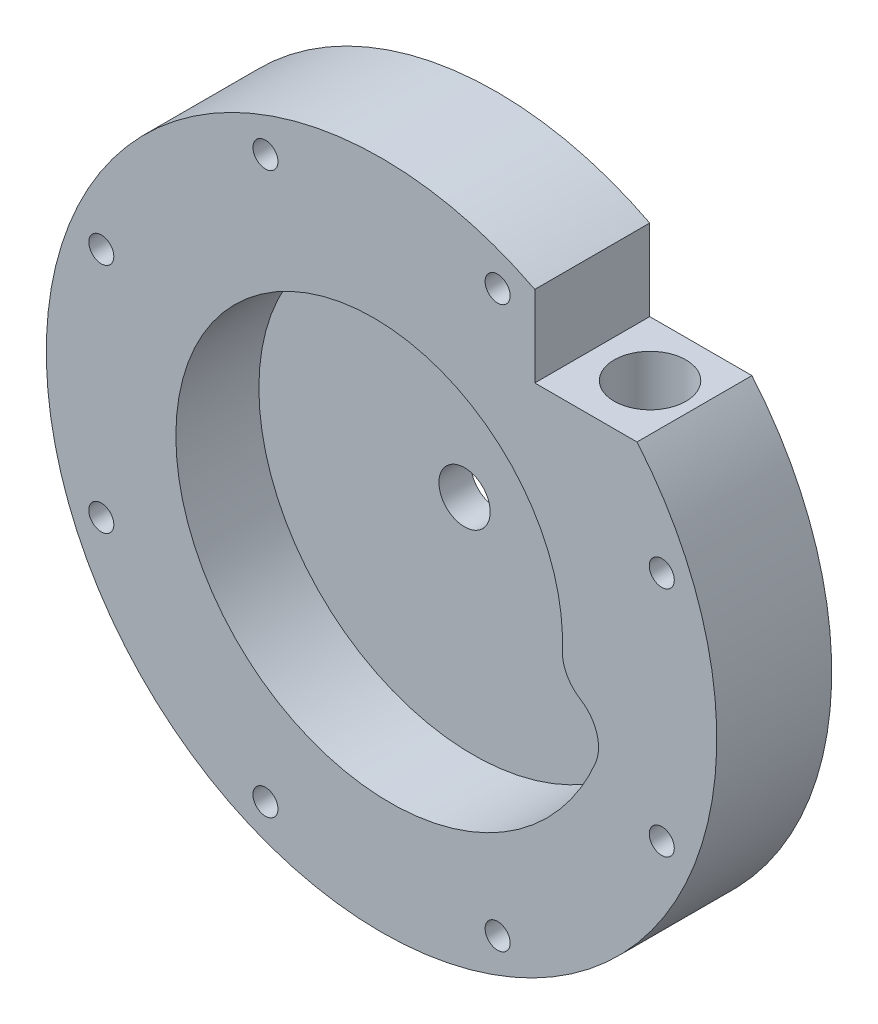
SolidWorks part; units mm, degrees
material "6061-T6 (SS)"
ref_plane "Front Plane" through (0, 0, 0) normal (0, 0, 1) x (1, 0, 0)
ref_plane "Top Plane" through (0, 0, 0) normal (0, 1, 0) x (1, 0, 0)
ref_plane "Right Plane" through (0, 0, 0) normal (1, 0, 0) x (0, 0, -1)
sketch "Sketch22" plane through (0, 0, 0) normal (0, 1, 0) x (1, 0, 0)
  line L0 (-25.4, 0) -> (-5.1, 0)
  line L1 (-25.4, 0) -> (-25.4, -16.51)
  line L2 (-17.4625, 6.35) -> (-17.4625, 4.7625)
  line L3 (-25.4, -16.51) -> (-66.675, -16.51)
  line L4 (-66.675, -16.51) -> (-66.675, 6.35)
  line L9 (-17.4625, 6.35) -> (-66.675, 6.35)
  line L10 (0, 0) -> (0, 9.525) construction
  line L11 (-5.1, 6.35) -> (-5.1, 0)
  line L12 (-17.4625, 4.7625) -> (-11.1125, 4.7625)
  line L15 (-11.1125, 4.7625) -> (-11.1125, 6.35)
  line L16 (-11.1125, 6.35) -> (-5.1, 6.35)
  line L17 (-25.4, -0.508) -> (-0.1653, -0.508) construction
  line L18 (-0.1653, -9.508) -> (-0.1653, -0.508) construction
  dimension "D5" = 50.8
  dimension "D6" = 133.35
  dimension "D7" = 10.2
  dimension "D2" = 6.35
  dimension "D4" = 22.225
  dimension "D8" = 1.5875
  dimension "D1" = 6.35
  dimension "D3" = 22.86
  dimension "D9" = 0.508
revolve "Main Body" add sketch "Sketch22" angle 360 about L10
curve "Volute Spiral"
  spline degree 3 poles (35.9487, 0, 0) (35.9516, 0.0754, 0) (35.9573, 0.2262, 0) (35.9642, 0.4524, 0) (35.9698, 0.6788, 0) (35.9739, 0.9052, 0) (35.9766, 1.1318, 0) (35.9779, 1.3583, 0) (35.9778, 1.585, 0) (35.9763, 1.8117, 0) (35.9733, 2.0385, 0) (35.969, 2.2653, 0) (35.9632, 2.4921, 0) (35.956, 2.7189, 0) (35.9473, 2.9457, 0) (35.9373, 3.1726, 0) (35.9258, 3.3994, 0) (35.9129, 3.6262, 0) (35.8986, 3.853, 0) (35.8828, 4.0798, 0) (35.8656, 4.3065, 0) (35.847, 4.5331, 0) (35.827, 4.7597, 0) (35.8055, 4.9862, 0) (35.7826, 5.2127, 0) (35.7583, 5.439, 0) (35.7326, 5.6653, 0) (35.7054, 5.8914, 0) (35.6768, 6.1174, 0) (35.6468, 6.3433, 0) (35.6153, 6.5691, 0) (35.5825, 6.7947, 0) (35.5482, 7.0201, 0) (35.5124, 7.2455, 0) (35.4753, 7.4706, 0) (35.4367, 7.6955, 0) (35.3967, 7.9203, 0) (35.3553, 8.1449, 0) (35.3125, 8.3692, 0) (35.2683, 8.5934, 0) (35.2226, 8.8173, 0) (35.1755, 9.041, 0) (35.127, 9.2644, 0) (35.0771, 9.4876, 0) (35.0257, 9.7105, 0) (34.973, 9.9332, 0) (34.9188, 10.1556, 0) (34.8633, 10.3777, 0) (34.8063, 10.5995, 0) (34.7479, 10.821, 0) (34.6881, 11.0422, 0) (34.6269, 11.263, 0) (34.5643, 11.4836, 0) (34.5004, 11.7037, 0) (34.435, 11.9236, 0) (34.3682, 12.1431, 0) (34.3, 12.3622, 0) (34.2304, 12.5809, 0) (34.1594, 12.7993, 0) (34.0871, 13.0172, 0) (34.0133, 13.2348, 0) (33.9382, 13.4519, 0) (33.8617, 13.6686, 0) (33.7838, 13.8849, 0) (33.7045, 14.1008, 0) (33.6238, 14.3162, 0) (33.5418, 14.5311, 0) (33.4584, 14.7456, 0) (33.3737, 14.9596, 0) (33.2875, 15.1732, 0) (33.2, 15.3862, 0) (33.1112, 15.5988, 0) (33.021, 15.8108, 0) (32.9294, 16.0223, 0) (32.8365, 16.2333, 0) (32.7422, 16.4438, 0) (32.6466, 16.6537, 0) (32.5497, 16.8631, 0) (32.4514, 17.0719, 0) (32.3517, 17.2801, 0) (32.2508, 17.4878, 0) (32.1485, 17.6949, 0) (32.0448, 17.9013, 0) (31.9399, 18.1072, 0) (31.8336, 18.3125, 0) (31.7261, 18.5171, 0) (31.6172, 18.7212, 0) (31.507, 18.9246, 0) (31.3955, 19.1273, 0) (31.2827, 19.3294, 0) (31.1685, 19.5308, 0) (31.0531, 19.7316, 0) (30.9365, 19.9317, 0) (30.8185, 20.1311, 0) (30.6992, 20.3298, 0) (30.5787, 20.5278, 0) (30.4569, 20.7251, 0) (30.3338, 20.9217, 0) (30.2094, 21.1175, 0) (30.0838, 21.3126, 0) (29.957, 21.507, 0) (29.8288, 21.7006, 0) (29.6995, 21.8935, 0) (29.5689, 22.0856, 0) (29.437, 22.2769, 0) (29.3039, 22.4674, 0) (29.1696, 22.6571, 0) (29.0341, 22.8461, 0) (28.8973, 23.0342, 0) (28.7593, 23.2215, 0) (28.6201, 23.408, 0) (28.4797, 23.5937, 0) (28.3381, 23.7785, 0) (28.1953, 23.9625, 0) (28.0514, 24.1456, 0) (27.9062, 24.3279, 0) (27.7598, 24.5093, 0) (27.6123, 24.6898, 0) (27.4636, 24.8694, 0) (27.3137, 25.0482, 0) (27.1627, 25.226, 0) (27.0105, 25.403, 0) (26.8572, 25.579, 0) (26.7027, 25.7541, 0) (26.5471, 25.9282, 0) (26.3903, 26.1015, 0) (26.2325, 26.2738, 0) (26.0735, 26.4451, 0) (25.9134, 26.6155, 0) (25.7521, 26.7849, 0) (25.5898, 26.9533, 0) (25.4264, 27.1208, 0) (25.2619, 27.2872, 0) (25.0963, 27.4527, 0) (24.9296, 27.6172, 0) (24.7618, 27.7806, 0) (24.593, 27.9431, 0) (24.4231, 28.1045, 0) (24.2521, 28.2649, 0) (24.0802, 28.4242, 0) (23.9071, 28.5825, 0) (23.733, 28.7398, 0) (23.5579, 28.896, 0) (23.3818, 29.0511, 0) (23.2046, 29.2052, 0) (23.0265, 29.3582, 0) (22.8473, 29.5101, 0) (22.6671, 29.6609, 0) (22.486, 29.8106, 0) (22.3038, 29.9592, 0) (22.1207, 30.1067, 0) (21.9366, 30.2531, 0) (21.7515, 30.3984, 0) (21.5655, 30.5425, 0) (21.3785, 30.6855, 0) (21.1906, 30.8274, 0) (21.0018, 30.9681, 0) (20.812, 31.1076, 0) (20.6213, 31.246, 0) (20.4297, 31.3833, 0) (20.2371, 31.5193, 0) (20.0437, 31.6542, 0) (19.8494, 31.7879, 0) (19.6541, 31.9204, 0) (19.458, 32.0517, 0) (19.2611, 32.1818, 0) (19.0632, 32.3106, 0) (18.8645, 32.4383, 0) (18.665, 32.5648, 0) (18.4646, 32.69, 0) (18.2634, 32.814, 0) (18.0613, 32.9368, 0) (17.8584, 33.0583, 0) (17.6547, 33.1786, 0) (17.4502, 33.2976, 0) (17.2449, 33.4154, 0) (17.0389, 33.5319, 0) (16.832, 33.6471, 0) (16.6244, 33.761, 0) (16.4159, 33.8737, 0) (16.2068, 33.9851, 0) (15.9969, 34.0952, 0) (15.7862, 34.204, 0) (15.5748, 34.3115, 0) (15.3627, 34.4177, 0) (15.1498, 34.5226, 0) (14.9363, 34.6262, 0) (14.722, 34.7285, 0) (14.5071, 34.8294, 0) (14.2914, 34.929, 0) (14.0751, 35.0273, 0) (13.8581, 35.1242, 0) (13.6405, 35.2198, 0) (13.4222, 35.3141, 0) (13.2032, 35.407, 0) (12.9836, 35.4985, 0) (12.7634, 35.5887, 0) (12.5426, 35.6775, 0) (12.3212, 35.765, 0) (12.0991, 35.8511, 0) (11.8765, 35.9358, 0) (11.6532, 36.0191, 0) (11.4294, 36.101, 0) (11.205, 36.1816, 0) (10.9801, 36.2607, 0) (10.7546, 36.3385, 0) (10.5286, 36.4148, 0) (10.302, 36.4898, 0) (10.0749, 36.5633, 0) (9.8473, 36.6355, 0) (9.6192, 36.7062, 0) (9.3906, 36.7755, 0) (9.1615, 36.8434, 0) (8.9319, 36.9098, 0) (8.7018, 36.9748, 0) (8.4713, 37.0384, 0) (8.2403, 37.1006, 0) (8.0089, 37.1613, 0) (7.777, 37.2206, 0) (7.5447, 37.2784, 0) (7.312, 37.3348, 0) (7.0789, 37.3897, 0) (6.8453, 37.4432, 0) (6.6114, 37.4952, 0) (6.3771, 37.5458, 0) (6.1424, 37.5949, 0) (5.9074, 37.6425, 0) (5.672, 37.6887, 0) (5.4362, 37.7334, 0) (5.2002, 37.7766, 0) (4.9637, 37.8183, 0) (4.727, 37.8586, 0) (4.49, 37.8974, 0) (4.2526, 37.9347, 0) (4.015, 37.9705, 0) (3.7771, 38.0048, 0) (3.5389, 38.0377, 0) (3.3004, 38.069, 0) (3.0617, 38.0989, 0) (2.8228, 38.1273, 0) (2.5836, 38.1541, 0) (2.3442, 38.1795, 0) (2.1046, 38.2034, 0) (1.8647, 38.2257, 0) (1.6247, 38.2466, 0) (1.3845, 38.2659, 0) (1.1441, 38.2838, 0) (0.9035, 38.3001, 0) (0.6628, 38.315, 0) (0.4219, 38.3283, 0) (0.1808, 38.3401, 0) (-0.0603, 38.3504, 0) (-0.3016, 38.3591, 0) (-0.543, 38.3664, 0) (-0.7845, 38.3721, 0) (-1.0261, 38.3764, 0) (-1.2677, 38.3791, 0) (-1.5095, 38.3802, 0) (-1.7513, 38.3799, 0) (-1.9932, 38.378, 0) (-2.2351, 38.3746, 0) (-2.477, 38.3697, 0) (-2.719, 38.3633, 0) (-2.961, 38.3554, 0) (-3.203, 38.3459, 0) (-3.445, 38.3349, 0) (-3.687, 38.3223, 0) (-3.929, 38.3083, 0) (-4.1709, 38.2927, 0) (-4.4128, 38.2756, 0) (-4.6546, 38.2569, 0) (-4.8964, 38.2368, 0) (-5.1381, 38.2151, 0) (-5.3798, 38.1919, 0) (-5.6213, 38.1671, 0) (-5.8628, 38.1408, 0) (-6.1041, 38.113, 0) (-6.3453, 38.0837, 0) (-6.5864, 38.0529, 0) (-6.8274, 38.0205, 0) (-7.0682, 37.9866, 0) (-7.3089, 37.9512, 0) (-7.5494, 37.9142, 0) (-7.7897, 37.8758, 0) (-8.0298, 37.8358, 0) (-8.2698, 37.7943, 0) (-8.5095, 37.7512, 0) (-8.749, 37.7067, 0) (-8.9883, 37.6606, 0) (-9.2274, 37.613, 0) (-9.4662, 37.5639, 0) (-9.7048, 37.5133, 0) (-9.9431, 37.4612, 0) (-10.1811, 37.4076, 0) (-10.4189, 37.3524, 0) (-10.6563, 37.2957, 0) (-10.8935, 37.2376, 0) (-11.1303, 37.1779, 0) (-11.3669, 37.1167, 0) (-11.6031, 37.054, 0) (-11.8389, 36.9898, 0) (-12.0745, 36.9241, 0) (-12.3096, 36.857, 0) (-12.5444, 36.7883, 0) (-12.7788, 36.7181, 0) (-13.0129, 36.6464, 0) (-13.2465, 36.5733, 0) (-13.4797, 36.4986, 0) (-13.7126, 36.4225, 0) (-13.9449, 36.3449, 0) (-14.1769, 36.2658, 0) (-14.4084, 36.1852, 0) (-14.6395, 36.1032, 0) (-14.8701, 36.0196, 0) (-15.1002, 35.9346, 0) (-15.3299, 35.8482, 0) (-15.559, 35.7602, 0) (-15.7877, 35.6708, 0) (-16.0159, 35.58, 0) (-16.2435, 35.4877, 0) (-16.4706, 35.3939, 0) (-16.6972, 35.2987, 0) (-16.9232, 35.202, 0) (-17.1487, 35.1039, 0) (-17.3736, 35.0043, 0) (-17.5979, 34.9033, 0) (-17.8217, 34.8009, 0) (-18.0448, 34.697, 0) (-18.2674, 34.5917, 0) (-18.4893, 34.485, 0) (-18.7107, 34.3769, 0) (-18.9314, 34.2673, 0) (-19.1514, 34.1563, 0) (-19.3708, 34.044, 0) (-19.5896, 33.9302, 0) (-19.8077, 33.815, 0) (-20.0251, 33.6984, 0) (-20.2419, 33.5804, 0) (-20.4579, 33.461, 0) (-20.6733, 33.3402, 0) (-20.8879, 33.218, 0) (-21.1018, 33.0945, 0) (-21.315, 32.9696, 0) (-21.5275, 32.8433, 0) (-21.7392, 32.7156, 0) (-21.9501, 32.5866, 0) (-22.1603, 32.4562, 0) (-22.3698, 32.3245, 0) (-22.5784, 32.1914, 0) (-22.7863, 32.057, 0) (-22.9933, 31.9212, 0) (-23.1996, 31.7841, 0) (-23.405, 31.6457, 0) (-23.6097, 31.5059, 0) (-23.8134, 31.3648, 0) (-24.0164, 31.2224, 0) (-24.2185, 31.0787, 0) (-24.4197, 30.9337, 0) (-24.6201, 30.7874, 0) (-24.8196, 30.6398, 0) (-25.0182, 30.4909, 0) (-25.216, 30.3407, 0) (-25.4128, 30.1892, 0) (-25.6087, 30.0365, 0) (-25.8037, 29.8825, 0) (-25.9978, 29.7272, 0) (-26.191, 29.5707, 0) (-26.3832, 29.4129, 0) (-26.5745, 29.2539, 0) (-26.7648, 29.0936, 0) (-26.9541, 28.9321, 0) (-27.1425, 28.7693, 0) (-27.3299, 28.6054, 0) (-27.5163, 28.4402, 0) (-27.7017, 28.2738, 0) (-27.8861, 28.1062, 0) (-28.0695, 27.9374, 0) (-28.2519, 27.7674, 0) (-28.4332, 27.5962, 0) (-28.6135, 27.4238, 0) (-28.7928, 27.2503, 0) (-28.971, 27.0756, 0) (-29.1482, 26.8997, 0) (-29.3243, 26.7227, 0) (-29.4993, 26.5445, 0) (-29.6733, 26.3652, 0) (-29.8461, 26.1847, 0) (-30.0179, 26.0031, 0) (-30.1885, 25.8204, 0) (-30.3581, 25.6366, 0) (-30.5265, 25.4516, 0) (-30.6938, 25.2656, 0) (-30.86, 25.0784, 0) (-31.025, 24.8902, 0) (-31.1889, 24.7009, 0) (-31.3516, 24.5105, 0) (-31.5132, 24.319, 0) (-31.6736, 24.1265, 0) (-31.8329, 23.9329, 0) (-31.9909, 23.7382, 0) (-32.1478, 23.5426, 0) (-32.3034, 23.3459, 0) (-32.4579, 23.1481, 0) (-32.6112, 22.9494, 0) (-32.7632, 22.7496, 0) (-32.914, 22.5489, 0) (-33.0636, 22.3471, 0) (-33.212, 22.1443, 0) (-33.3591, 21.9406, 0) (-33.505, 21.7359, 0) (-33.6496, 21.5302, 0) (-33.7929, 21.3236, 0) (-33.935, 21.116, 0) (-34.0758, 20.9075, 0) (-34.2154, 20.698, 0) (-34.3536, 20.4876, 0) (-34.4906, 20.2763, 0) (-34.6262, 20.0641, 0) (-34.7606, 19.851, 0) (-34.8936, 19.637, 0) (-35.0253, 19.4221, 0) (-35.1557, 19.2063, 0) (-35.2848, 18.9896, 0) (-35.4126, 18.7721, 0) (-35.539, 18.5537, 0) (-35.664, 18.3345, 0) (-35.7877, 18.1144, 0) (-35.9101, 17.8935, 0) (-36.0311, 17.6718, 0) (-36.1507, 17.4493, 0) (-36.2689, 17.2259, 0) (-36.3858, 17.0018, 0) (-36.5013, 16.7769, 0) (-36.6154, 16.5512, 0) (-36.7281, 16.3247, 0) (-36.8394, 16.0975, 0) (-36.9493, 15.8695, 0) (-37.0578, 15.6408, 0) (-37.1649, 15.4113, 0) (-37.2705, 15.1811, 0) (-37.3748, 14.9502, 0) (-37.4776, 14.7186, 0) (-37.5789, 14.4862, 0) (-37.6789, 14.2532, 0) (-37.7773, 14.0195, 0) (-37.8744, 13.7851, 0) (-37.97, 13.5501, 0) (-38.0641, 13.3144, 0) (-38.1567, 13.078, 0) (-38.2479, 12.8411, 0) (-38.3377, 12.6034, 0) (-38.4259, 12.3652, 0) (-38.5127, 12.1264, 0) (-38.598, 11.8869, 0) (-38.6818, 11.6469, 0) (-38.7641, 11.4062, 0) (-38.8449, 11.165, 0) (-38.9242, 10.9233, 0) (-39.002, 10.6809, 0) (-39.0783, 10.4381, 0) (-39.1531, 10.1947, 0) (-39.2264, 9.9507, 0) (-39.2982, 9.7063, 0) (-39.3684, 9.4613, 0) (-39.4371, 9.2159, 0) (-39.5043, 8.9699, 0) (-39.57, 8.7235, 0) (-39.6341, 8.4766, 0) (-39.6966, 8.2292, 0) (-39.7577, 7.9814, 0) (-39.8172, 7.7332, 0) (-39.8751, 7.4845, 0) (-39.9315, 7.2354, 0) (-39.9863, 6.9858, 0) (-40.0396, 6.7359, 0) (-40.0913, 6.4856, 0) (-40.1414, 6.2349, 0) (-40.19, 5.9838, 0) (-40.237, 5.7324, 0) (-40.2825, 5.4806, 0) (-40.3263, 5.2284, 0) (-40.3686, 4.976, 0) (-40.4093, 4.7232, 0) (-40.4484, 4.47, 0) (-40.486, 4.2166, 0) (-40.5219, 3.9629, 0) (-40.5563, 3.7089, 0) (-40.5891, 3.4546, 0) (-40.6203, 3.2001, 0) (-40.6498, 2.9453, 0) (-40.6778, 2.6902, 0) (-40.7042, 2.435, 0) (-40.729, 2.1795, 0) (-40.7522, 1.9237, 0) (-40.7738, 1.6678, 0) (-40.7937, 1.4117, 0) (-40.8121, 1.1554, 0) (-40.8289, 0.8989, 0) (-40.844, 0.6423, 0) (-40.8575, 0.3855, 0) (-40.8695, 0.1285, 0) (-40.8798, -0.1286, 0) (-40.8884, -0.3858, 0) (-40.8955, -0.6431, 0) (-40.901, -0.9005, 0) (-40.9048, -1.158, 0) (-40.907, -1.4156, 0) (-40.9076, -1.6733, 0) (-40.9066, -1.931, 0) (-40.9039, -2.1888, 0) (-40.8996, -2.4467, 0) (-40.8937, -2.7045, 0) (-40.8862, -2.9624, 0) (-40.8771, -3.2203, 0) (-40.8663, -3.4782, 0) (-40.8539, -3.7361, 0) (-40.8399, -3.994, 0) (-40.8242, -4.2519, 0) (-40.8069, -4.5097, 0) (-40.788, -4.7674, 0) (-40.7675, -5.0251, 0) (-40.7453, -5.2828, 0) (-40.7215, -5.5403, 0) (-40.6961, -5.7978, 0) (-40.669, -6.0552, 0) (-40.6404, -6.3124, 0) (-40.6101, -6.5695, 0) (-40.5781, -6.8265, 0) (-40.5446, -7.0834, 0) (-40.5094, -7.3401, 0) (-40.4726, -7.5967, 0) (-40.4342, -7.853, 0) (-40.3941, -8.1092, 0) (-40.3525, -8.3652, 0) (-40.3092, -8.621, 0) (-40.2643, -8.8766, 0) (-40.2177, -9.1319, 0) (-40.1696, -9.3871, 0) (-40.1198, -9.6419, 0) (-40.0684, -9.8966, 0) (-40.0154, -10.1509, 0) (-39.9608, -10.405, 0) (-39.9046, -10.6588, 0) (-39.8468, -10.9123, 0) (-39.7873, -11.1655, 0) (-39.7263, -11.4184, 0) (-39.6636, -11.6709, 0) (-39.5994, -11.9232, 0) (-39.5335, -12.175, 0) (-39.466, -12.4265, 0) (-39.397, -12.6777, 0) (-39.3263, -12.9285, 0) (-39.254, -13.1789, 0) (-39.1802, -13.4288, 0) (-39.1048, -13.6784, 0) (-39.0277, -13.9276, 0) (-38.9491, -14.1763, 0) (-38.8689, -14.4246, 0) (-38.7871, -14.6725, 0) (-38.7038, -14.9199, 0) (-38.6188, -15.1668, 0) (-38.5323, -15.4132, 0) (-38.4442, -15.6592, 0) (-38.3546, -15.9047, 0) (-38.2634, -16.1496, 0) (-38.1706, -16.3941, 0) (-38.0762, -16.638, 0) (-37.9803, -16.8813, 0) (-37.8829, -17.1242, 0) (-37.7839, -17.3664, 0) (-37.6833, -17.6081, 0) (-37.5812, -17.8492, 0) (-37.4776, -18.0898, 0) (-37.3724, -18.3297, 0) (-37.2657, -18.569, 0) (-37.1574, -18.8077, 0) (-37.0477, -19.0458, 0) (-36.9364, -19.2833, 0) (-36.8236, -19.5201, 0) (-36.7092, -19.7562, 0) (-36.5934, -19.9917, 0) (-36.476, -20.2265, 0) (-36.3572, -20.4606, 0) (-36.2368, -20.694, 0) (-36.1149, -20.9268, 0) (-35.9916, -21.1588, 0) (-35.8667, -21.3901, 0) (-35.7404, -21.6206, 0) (-35.6126, -21.8504, 0) (-35.4833, -22.0795, 0) (-35.3526, -22.3078, 0) (-35.2203, -22.5353, 0) (-35.0867, -22.762, 0) (-34.9515, -22.988, 0) (-34.8149, -23.2131, 0) (-34.6769, -23.4375, 0) (-34.5374, -23.661, 0) (-34.3964, -23.8837, 0) (-34.2541, -24.1056, 0) (-34.1103, -24.3266, 0) (-33.9651, -24.5468, 0) (-33.8184, -24.7661, 0) (-33.6704, -24.9845, 0) (-33.5209, -25.202, 0) (-33.3701, -25.4187, 0) (-33.2178, -25.6345, 0) (-33.0641, -25.8493, 0) (-32.9091, -26.0632, 0) (-32.7527, -26.2762, 0) (-32.5949, -26.4883, 0) (-32.4357, -26.6994, 0) (-32.2751, -26.9096, 0) (-32.1132, -27.1188, 0) (-31.95, -27.327, 0) (-31.7854, -27.5343, 0) (-31.6194, -27.7405, 0) (-31.4522, -27.9458, 0) (-31.2835, -28.15, 0) (-31.1136, -28.3533, 0) (-30.9424, -28.5555, 0) (-30.7698, -28.7567, 0) (-30.5959, -28.9568, 0) (-30.4207, -29.1559, 0) (-30.2443, -29.354, 0) (-30.0665, -29.5509, 0) (-29.8875, -29.7468, 0) (-29.7072, -29.9417, 0) (-29.5256, -30.1354, 0) (-29.3428, -30.328, 0) (-29.1587, -30.5195, 0) (-28.9733, -30.7099, 0) (-28.7867, -30.8992, 0) (-28.5989, -31.0874, 0) (-28.4099, -31.2744, 0) (-28.2196, -31.4602, 0) (-28.0281, -31.6449, 0) (-27.8354, -31.8285, 0) (-27.6416, -32.0109, 0) (-27.4465, -32.1921, 0) (-27.2502, -32.3721, 0) (-27.0528, -32.5509, 0) (-26.8542, -32.7285, 0) (-26.6544, -32.9049, 0) (-26.4535, -33.0801, 0) (-26.2514, -33.254, 0) (-26.0482, -33.4267, 0) (-25.8438, -33.5982, 0) (-25.6383, -33.7685, 0) (-25.4317, -33.9374, 0) (-25.224, -34.1052, 0) (-25.0152, -34.2716, 0) (-24.8053, -34.4368, 0) (-24.5943, -34.6007, 0) (-24.3822, -34.7633, 0) (-24.1691, -34.9246, 0) (-23.9549, -35.0846, 0) (-23.7396, -35.2432, 0) (-23.5233, -35.4006, 0) (-23.3059, -35.5566, 0) (-23.0876, -35.7113, 0) (-22.8681, -35.8647, 0) (-22.6477, -36.0167, 0) (-22.4263, -36.1674, 0) (-22.2039, -36.3167, 0) (-21.9804, -36.4646, 0) (-21.756, -36.6112, 0) (-21.5306, -36.7564, 0) (-21.3043, -36.9002, 0) (-21.077, -37.0426, 0) (-20.8488, -37.1836, 0) (-20.6196, -37.3232, 0) (-20.3894, -37.4614, 0) (-20.1584, -37.5981, 0) (-19.9264, -37.7335, 0) (-19.6936, -37.8674, 0) (-19.4598, -37.9999, 0) (-19.2252, -38.1309, 0) (-18.9897, -38.2605, 0) (-18.7533, -38.3886, 0) (-18.516, -38.5153, 0) (-18.2779, -38.6405, 0) (-18.039, -38.7643, 0) (-17.7992, -38.8866, 0) (-17.5586, -39.0073, 0) (-17.3172, -39.1266, 0) (-17.075, -39.2444, 0) (-16.8319, -39.3607, 0) (-16.5881, -39.4755, 0) (-16.3436, -39.5888, 0) (-16.0982, -39.7006, 0) (-15.8521, -39.8109, 0) (-15.6052, -39.9196, 0) (-15.3576, -40.0268, 0) (-15.1093, -40.1325, 0) (-14.8602, -40.2366, 0) (-14.6105, -40.3392, 0) (-14.36, -40.4402, 0) (-14.1088, -40.5397, 0) (-13.857, -40.6377, 0) (-13.6045, -40.734, 0) (-13.3513, -40.8288, 0) (-13.0975, -40.922, 0) (-12.843, -41.0137, 0) (-12.5879, -41.1037, 0) (-12.3321, -41.1922, 0) (-12.0758, -41.2791, 0) (-11.8188, -41.3644, 0) (-11.5613, -41.4481, 0) (-11.3031, -41.5302, 0) (-11.0444, -41.6106, 0) (-10.7851, -41.6895, 0) (-10.5253, -41.7668, 0) (-10.2649, -41.8424, 0) (-10.004, -41.9164, 0) (-9.7426, -41.9888, 0) (-9.4806, -42.0596, 0) (-9.2182, -42.1287, 0) (-8.9552, -42.1962, 0) (-8.6918, -42.262, 0) (-8.4279, -42.3262, 0) (-8.1635, -42.3888, 0) (-7.8987, -42.4497, 0) (-7.6334, -42.509, 0) (-7.3677, -42.5666, 0) (-7.1016, -42.6225, 0) (-6.835, -42.6768, 0) (-6.5681, -42.7294, 0) (-6.3007, -42.7803, 0) (-6.033, -42.8296, 0) (-5.7649, -42.8772, 0) (-5.4965, -42.9231, 0) (-5.2277, -42.9673, 0) (-4.9586, -43.0099, 0) (-4.6891, -43.0508, 0) (-4.4194, -43.0899, 0) (-4.1493, -43.1274, 0) (-3.8789, -43.1632, 0) (-3.6082, -43.1973, 0) (-3.3373, -43.2298, 0) (-3.0661, -43.2605, 0) (-2.7946, -43.2895, 0) (-2.5229, -43.3168, 0) (-2.251, -43.3424, 0) (-1.9788, -43.3663, 0) (-1.7064, -43.3885, 0) (-1.4339, -43.4089, 0) (-1.1611, -43.4277, 0) (-0.8882, -43.4448, 0) (-0.615, -43.4601, 0) (-0.3418, -43.4737, 0) (-0.0684, -43.4856, 0) (0.2052, -43.4958, 0) (0.4789, -43.5043, 0) (0.7527, -43.511, 0) (1.0266, -43.516, 0) (1.3005, -43.5193, 0) (1.5746, -43.5209, 0) (1.8488, -43.5208, 0) (2.123, -43.5189, 0) (2.3972, -43.5153, 0) (2.6715, -43.5099, 0) (2.9458, -43.5029, 0) (3.2201, -43.4941, 0) (3.4945, -43.4836, 0) (3.7688, -43.4713, 0) (4.0431, -43.4574, 0) (4.3174, -43.4417, 0) (4.5917, -43.4242, 0) (4.8659, -43.405, 0) (5.1401, -43.3841, 0) (5.4141, -43.3615, 0) (5.6881, -43.3372, 0) (5.962, -43.3111, 0) (6.2358, -43.2832, 0) (6.5095, -43.2537, 0) (6.7831, -43.2224, 0) (7.0565, -43.1894, 0) (7.3298, -43.1547, 0) (7.6029, -43.1182, 0) (7.8759, -43.08, 0) (8.1486, -43.0401, 0) (8.4212, -42.9984, 0) (8.6936, -42.955, 0) (8.9658, -42.9099, 0) (9.2377, -42.8631, 0) (9.5094, -42.8146, 0) (9.7809, -42.7643, 0) (10.0521, -42.7123, 0) (10.3231, -42.6586, 0) (10.5937, -42.6032, 0) (10.8641, -42.546, 0) (11.1342, -42.4872, 0) (11.4039, -42.4266, 0) (11.6734, -42.3643, 0) (11.9425, -42.3003, 0) (12.2113, -42.2346, 0) (12.4797, -42.1672, 0) (12.7477, -42.0981, 0) (13.0154, -42.0273, 0) (13.2827, -41.9548, 0) (13.5496, -41.8805, 0) (13.8161, -41.8046, 0) (14.0822, -41.727, 0) (14.3478, -41.6477, 0) (14.613, -41.5667, 0) (14.8777, -41.4841, 0) (15.142, -41.3997, 0) (15.4058, -41.3136, 0) (15.6692, -41.2259, 0) (15.932, -41.1365, 0) (16.1943, -41.0454, 0) (16.4562, -40.9527, 0) (16.7174, -40.8583, 0) (16.9782, -40.7622, 0) (17.2384, -40.6644, 0) (17.498, -40.565, 0) (17.7571, -40.4639, 0) (18.0156, -40.3612, 0) (18.2735, -40.2568, 0) (18.5309, -40.1508, 0) (18.7876, -40.0432, 0) (19.0436, -39.9339, 0) (19.2991, -39.8229, 0) (19.5539, -39.7104, 0) (19.808, -39.5962, 0) (20.0615, -39.4803, 0) (20.3144, -39.3629, 0) (20.5665, -39.2438, 0) (20.8179, -39.1231, 0) (21.0687, -39.0008, 0) (21.3187, -38.877, 0) (21.568, -38.7515, 0) (21.8166, -38.6244, 0) (22.0644, -38.4957, 0) (22.3114, -38.3654, 0) (22.5577, -38.2335, 0) (22.8033, -38.1001, 0) (23.048, -37.9651, 0) (23.2919, -37.8285, 0) (23.5351, -37.6903, 0) (23.7774, -37.5506, 0) (24.0189, -37.4094, 0) (24.2595, -37.2665, 0) (24.4993, -37.1222, 0) (24.7383, -36.9762, 0) (24.9764, -36.8288, 0) (25.2136, -36.6798, 0) (25.4499, -36.5293, 0) (25.6854, -36.3773, 0) (25.9199, -36.2237, 0) (26.1535, -36.0687, 0) (26.3862, -35.9121, 0) (26.6179, -35.7541, 0) (26.8487, -35.5945, 0) (27.0786, -35.4335, 0) (27.3075, -35.271, 0) (27.5354, -35.1069, 0) (27.7623, -34.9415, 0) (27.9883, -34.7745, 0) (28.2132, -34.6061, 0) (28.4372, -34.4363, 0) (28.6601, -34.265, 0) (28.882, -34.0923, 0) (29.1028, -33.9181, 0) (29.3226, -33.7425, 0) (29.5413, -33.5655, 0) (29.759, -33.387, 0) (29.9756, -33.2072, 0) (30.1911, -33.0259, 0) (30.4055, -32.8433, 0) (30.6188, -32.6592, 0) (30.831, -32.4738, 0) (31.0421, -32.287, 0) (31.2521, -32.0988, 0) (31.4609, -31.9093, 0) (31.6686, -31.7184, 0) (31.8751, -31.5261, 0) (32.0804, -31.3326, 0) (32.2846, -31.1376, 0) (32.4876, -30.9414, 0) (32.6894, -30.7438, 0) (32.89, -30.5449, 0) (33.0894, -30.3447, 0) (33.2875, -30.1433, 0) (33.4845, -29.9405, 0) (33.6802, -29.7364, 0) (33.8747, -29.5311, 0) (34.0679, -29.3244, 0) (34.2599, -29.1166, 0) (34.4506, -28.9074, 0) (34.64, -28.6971, 0) (34.8281, -28.4855, 0) (35.015, -28.2726, 0) (35.2005, -28.0585, 0) (35.3848, -27.8433, 0) (35.5677, -27.6268, 0) (35.7493, -27.4091, 0) (35.9296, -27.1902, 0) (36.1085, -26.9701, 0) (36.2861, -26.7489, 0) (36.4623, -26.5265, 0) (36.6372, -26.3029, 0) (36.8107, -26.0782, 0) (36.9828, -25.8523, 0) (37.1536, -25.6254, 0) (37.3229, -25.3972, 0) (37.4909, -25.168, 0) (37.6574, -24.9377, 0) (37.8226, -24.7062, 0) (37.9863, -24.4737, 0) (38.1486, -24.2401, 0) (38.3094, -24.0054, 0) (38.4688, -23.7697, 0) (38.6268, -23.5329, 0) (38.7833, -23.295, 0) (38.9383, -23.0561, 0) (39.0919, -22.8162, 0) (39.2439, -22.5753, 0) (39.3945, -22.3333, 0) (39.5437, -22.0904, 0) (39.6913, -21.8465, 0) (39.8374, -21.6015, 0) (39.982, -21.3557, 0) (40.1251, -21.1088, 0) (40.2666, -20.861, 0) (40.4067, -20.6122, 0) (40.5452, -20.3625, 0) (40.6821, -20.1119, 0) (40.8175, -19.8604, 0) (40.9514, -19.6079, 0) (41.0837, -19.3546, 0) (41.2144, -19.1004, 0) (41.3436, -18.8453, 0) (41.4711, -18.5893, 0) (41.5971, -18.3325, 0) (41.7215, -18.0748, 0) (41.8444, -17.8162, 0) (41.9656, -17.5569, 0) (42.0852, -17.2967, 0) (42.2031, -17.0357, 0) (42.3195, -16.7739, 0) (42.4343, -16.5114, 0) (42.5474, -16.248, 0) (42.6589, -15.9839, 0) (42.7687, -15.719, 0) (42.8769, -15.4534, 0) (42.9835, -15.187, 0) (43.0884, -14.9199, 0) (43.1916, -14.6521, 0) (43.2932, -14.3836, 0) (43.3931, -14.1144, 0) (43.4913, -13.8444, 0) (43.5879, -13.5739, 0) (43.6828, -13.3026, 0) (43.776, -13.0307, 0) (43.8675, -12.7581, 0) (43.9573, -12.4849, 0) (44.0454, -12.2111, 0) (44.1318, -11.9367, 0) (44.2164, -11.6617, 0) (44.2994, -11.386, 0) (44.3807, -11.1098, 0) (44.4602, -10.833, 0) (44.538, -10.5557, 0) (44.6141, -10.2778, 0) (44.6884, -9.9994, 0) (44.761, -9.7204, 0) (44.8319, -9.4409, 0) (44.901, -9.1609, 0) (44.9684, -8.8805, 0) (45.034, -8.5995, 0) (45.0979, -8.3181, 0) (45.16, -8.0362, 0) (45.2204, -7.7538, 0) (45.279, -7.471, 0) (45.3358, -7.1878, 0) (45.3908, -6.9041, 0) (45.4441, -6.6201, 0) (45.4956, -6.3356, 0) (45.5453, -6.0508, 0) (45.5932, -5.7656, 0) (45.6394, -5.48, 0) (45.6837, -5.1941, 0) (45.7263, -4.9078, 0) (45.7671, -4.6212, 0) (45.8061, -4.3343, 0) (45.8432, -4.0471, 0) (45.8786, -3.7596, 0) (45.9122, -3.4717, 0) (45.944, -3.1837, 0) (45.9739, -2.8953, 0) (46.0021, -2.6067, 0) (46.0284, -2.3179, 0) (46.053, -2.0288, 0) (46.0757, -1.7396, 0) (46.0966, -1.4501, 0) (46.1157, -1.1604, 0) (46.133, -0.8705, 0) (46.1484, -0.5805, 0) (46.1621, -0.2903, 0) (46.1697, -0.0968, 0) (46.1735, 0, 0) knots 0 0 0 0 0.000879 0.001759 0.002638 0.003518 0.004398 0.005279 0.006159 0.00704 0.007921 0.008802 0.009684 0.010565 0.011447 0.012329 0.013212 0.014094 0.014977 0.01586 0.016744 0.017627 0.018511 0.019395 0.020279 0.021163 0.022048 0.022933 0.023818 0.024703 0.025589 0.026475 0.027361 0.028247 0.029133 0.03002 0.030907 0.031794 0.032681 0.033569 0.034457 0.035345 0.036233 0.037122 0.03801 0.038899 0.039789 0.040678 0.041568 0.042458 0.043348 0.044238 0.045129 0.04602 0.046911 0.047802 0.048693 0.049585 0.050477 0.051369 0.052262 0.053154 0.054047 0.05494 0.055834 0.056727 0.057621 0.058515 0.05941 0.060304 0.061199 0.062094 0.062989 0.063884 0.06478 0.065676 0.066572 0.067469 0.068365 0.069262 0.070159 0.071056 0.071954 0.072852 0.07375 0.074648 0.075546 0.076445 0.077344 0.078243 0.079143 0.080042 0.080942 0.081842 0.082743 0.083643 0.084544 0.085445 0.086346 0.087248 0.08815 0.089052 0.089954 0.090856 0.091759 0.092662 0.093565 0.094468 0.095372 0.096276 0.09718 0.098084 0.098989 0.099894 0.100799 0.101704 0.102609 0.103515 0.104421 0.105327 0.106234 0.10714 0.108047 0.108954 0.109862 0.110769 0.111677 0.112585 0.113494 0.114402 0.115311 0.11622 0.117129 0.118039 0.118948 0.119858 0.120769 0.121679 0.12259 0.123501 0.124412 0.125323 0.126235 0.127147 0.128059 0.128971 0.129884 0.130797 0.13171 0.132623 0.133536 0.13445 0.135364 0.136278 0.137193 0.138108 0.139023 0.139938 0.140853 0.141769 0.142685 0.143601 0.144517 0.145434 0.146351 0.147268 0.148185 0.149103 0.15002 0.150938 0.151857 0.152775 0.153694 0.154613 0.155532 0.156452 0.157371 0.158291 0.159212 0.160132 0.161053 0.161974 0.162895 0.163816 0.164738 0.16566 0.166582 0.167504 0.168427 0.169349 0.170272 0.171196 0.172119 0.173043 0.173967 0.174891 0.175816 0.176741 0.177666 0.178591 0.179516 0.180442 0.181368 0.182294 0.18322 0.184147 0.185074 0.186001 0.186928 0.187856 0.188784 0.189712 0.19064 0.191569 0.192498 0.193427 0.194356 0.195286 0.196215 0.197145 0.198076 0.199006 0.199937 0.200868 0.201799 0.20273 0.203662 0.204594 0.205526 0.206459 0.207391 0.208324 0.209257 0.210191 0.211124 0.212058 0.212992 0.213927 0.214861 0.215796 0.216731 0.217667 0.218602 0.219538 0.220474 0.22141 0.222347 0.223284 0.224221 0.225158 0.226095 0.227033 0.227971 0.228909 0.229848 0.230787 0.231726 0.232665 0.233604 0.234544 0.235484 0.236424 0.237364 0.238305 0.239246 0.240187 0.241128 0.24207 0.243012 0.243954 0.244896 0.245839 0.246782 0.247725 0.248668 0.249612 0.250556 0.2515 0.252444 0.253389 0.254333 0.255278 0.256224 0.257169 0.258115 0.259061 0.260007 0.260954 0.2619 0.262847 0.263795 0.264742 0.26569 0.266638 0.267586 0.268534 0.269483 0.270432 0.271381 0.272331 0.27328 0.27423 0.27518 0.276131 0.277081 0.278032 0.278983 0.279935 0.280886 0.281838 0.28279 0.283743 0.284695 0.285648 0.286601 0.287555 0.288508 0.289462 0.290416 0.29137 0.292325 0.29328 0.294235 0.29519 0.296146 0.297102 0.298058 0.299014 0.29997 0.300927 0.301884 0.302841 0.303799 0.304757 0.305715 0.306673 0.307631 0.30859 0.309549 0.310508 0.311468 0.312428 0.313388 0.314348 0.315308 0.316269 0.31723 0.318191 0.319152 0.320114 0.321076 0.322038 0.323001 0.323963 0.324926 0.325889 0.326853 0.327817 0.32878 0.329745 0.330709 0.331674 0.332639 0.333604 0.334569 0.335535 0.336501 0.337467 0.338433 0.3394 0.340367 0.341334 0.342301 0.343269 0.344237 0.345205 0.346173 0.347142 0.34811 0.34908 0.350049 0.351019 0.351988 0.352958 0.353929 0.354899 0.35587 0.356841 0.357813 0.358784 0.359756 0.360728 0.3617 0.362673 0.363646 0.364619 0.365592 0.366566 0.367539 0.368514 0.369488 0.370462 0.371437 0.372412 0.373388 0.374363 0.375339 0.376315 0.377291 0.378268 0.379245 0.380222 0.381199 0.382176 0.383154 0.384132 0.38511 0.386089 0.387068 0.388047 0.389026 0.390006 0.390985 0.391965 0.392946 0.393926 0.394907 0.395888 0.396869 0.397851 0.398833 0.399815 0.400797 0.401779 0.402762 0.403745 0.404728 0.405712 0.406696 0.40768 0.408664 0.409648 0.410633 0.411618 0.412603 0.413589 0.414575 0.415561 0.416547 0.417534 0.41852 0.419507 0.420495 0.421482 0.42247 0.423458 0.424446 0.425435 0.426423 0.427412 0.428402 0.429391 0.430381 0.431371 0.432361 0.433352 0.434343 0.435334 0.436325 0.437316 0.438308 0.4393 0.440292 0.441285 0.442278 0.443271 0.444264 0.445258 0.446251 0.447245 0.44824 0.449234 0.450229 0.451224 0.452219 0.453215 0.454211 0.455207 0.456203 0.457199 0.458196 0.459193 0.460191 0.461188 0.462186 0.463184 0.464182 0.465181 0.46618 0.467179 0.468178 0.469177 0.470177 0.471177 0.472178 0.473178 0.474179 0.47518 0.476181 0.477183 0.478185 0.479187 0.480189 0.481192 0.482195 0.483198 0.484201 0.485205 0.486209 0.487213 0.488217 0.489222 0.490226 0.491232 0.492237 0.493243 0.494248 0.495255 0.496261 0.497267 0.498274 0.499281 0.500289 0.501297 0.502304 0.503313 0.504321 0.50533 0.506338 0.507348 0.508357 0.509367 0.510377 0.511387 0.512397 0.513408 0.514419 0.51543 0.516441 0.517453 0.518465 0.519477 0.52049 0.521502 0.522515 0.523528 0.524542 0.525556 0.52657 0.527584 0.528598 0.529613 0.530628 0.531643 0.532659 0.533674 0.53469 0.535707 0.536723 0.53774 0.538757 0.539774 0.540792 0.54181 0.542828 0.543846 0.544864 0.545883 0.546902 0.547921 0.548941 0.549961 0.550981 0.552001 0.553022 0.554043 0.555064 0.556085 0.557107 0.558128 0.559151 0.560173 0.561196 0.562218 0.563241 0.564265 0.565288 0.566312 0.567336 0.568361 0.569386 0.57041 0.571436 0.572461 0.573487 0.574513 0.575539 0.576565 0.577592 0.578619 0.579646 0.580673 0.581701 0.582729 0.583757 0.584786 0.585815 0.586844 0.587873 0.588902 0.589932 0.590962 0.591992 0.593023 0.594054 0.595085 0.596116 0.597147 0.598179 0.599211 0.600244 0.601276 0.602309 0.603342 0.604375 0.605409 0.606443 0.607477 0.608511 0.609546 0.610581 0.611616 0.612651 0.613687 0.614723 0.615759 0.616795 0.617832 0.618869 0.619906 0.620943 0.621981 0.623019 0.624057 0.625096 0.626134 0.627173 0.628213 0.629252 0.630292 0.631332 0.632372 0.633413 0.634453 0.635494 0.636536 0.637577 0.638619 0.639661 0.640703 0.641746 0.642789 0.643832 0.644875 0.645919 0.646963 0.648007 0.649051 0.650096 0.651141 0.652186 0.653231 0.654277 0.655323 0.656369 0.657415 0.658462 0.659509 0.660556 0.661604 0.662651 0.663699 0.664748 0.665796 0.666845 0.667894 0.668943 0.669993 0.671042 0.672092 0.673143 0.674193 0.675244 0.676295 0.677346 0.678398 0.67945 0.680502 0.681554 0.682607 0.68366 0.684713 0.685766 0.68682 0.687874 0.688928 0.689982 0.691037 0.692092 0.693147 0.694203 0.695258 0.696314 0.697371 0.698427 0.699484 0.700541 0.701598 0.702656 0.703713 0.704771 0.70583 0.706888 0.707947 0.709006 0.710066 0.711125 0.712185 0.713245 0.714305 0.715366 0.716427 0.717488 0.71855 0.719611 0.720673 0.721735 0.722798 0.72386 0.724923 0.725987 0.72705 0.728114 0.729178 0.730242 0.731307 0.732371 0.733436 0.734502 0.735567 0.736633 0.737699 0.738766 0.739832 0.740899 0.741966 0.743033 0.744101 0.745169 0.746237 0.747306 0.748374 0.749443 0.750512 0.751582 0.752652 0.753722 0.754792 0.755862 0.756933 0.758004 0.759075 0.760147 0.761219 0.762291 0.763363 0.764436 0.765508 0.766582 0.767655 0.768729 0.769802 0.770877 0.771951 0.773026 0.774101 0.775176 0.776251 0.777327 0.778403 0.779479 0.780556 0.781632 0.782709 0.783787 0.784864 0.785942 0.78702 0.788098 0.789177 0.790256 0.791335 0.792414 0.793494 0.794574 0.795654 0.796734 0.797815 0.798896 0.799977 0.801058 0.80214 0.803222 0.804304 0.805387 0.806469 0.807552 0.808636 0.809719 0.810803 0.811887 0.812971 0.814056 0.815141 0.816226 0.817311 0.818397 0.819483 0.820569 0.821655 0.822742 0.823829 0.824916 0.826004 0.827091 0.828179 0.829268 0.830356 0.831445 0.832534 0.833623 0.834713 0.835803 0.836893 0.837983 0.839074 0.840165 0.841256 0.842347 0.843439 0.844531 0.845623 0.846715 0.847808 0.848901 0.849994 0.851088 0.852181 0.853275 0.85437 0.855464 0.856559 0.857654 0.858749 0.859845 0.860941 0.862037 0.863133 0.86423 0.865327 0.866424 0.867521 0.868619 0.869717 0.870815 0.871914 0.873013 0.874112 0.875211 0.87631 0.87741 0.87851 0.879611 0.880711 0.881812 0.882913 0.884014 0.885116 0.886218 0.88732 0.888423 0.889525 0.890628 0.891732 0.892835 0.893939 0.895043 0.896147 0.897252 0.898356 0.899461 0.900567 0.901672 0.902778 0.903884 0.904991 0.906097 0.907204 0.908311 0.909419 0.910527 0.911635 0.912743 0.913851 0.91496 0.916069 0.917178 0.918288 0.919398 0.920508 0.921618 0.922729 0.92384 0.924951 0.926062 0.927174 0.928286 0.929398 0.93051 0.931623 0.932736 0.933849 0.934963 0.936077 0.937191 0.938305 0.93942 0.940534 0.941649 0.942765 0.94388 0.944996 0.946113 0.947229 0.948346 0.949463 0.95058 0.951697 0.952815 0.953933 0.955051 0.95617 0.957289 0.958408 0.959527 0.960647 0.961767 0.962887 0.964007 0.965128 0.966249 0.96737 0.968491 0.969613 0.970735 0.971857 0.97298 0.974103 0.975226 0.976349 0.977473 0.978596 0.979721 0.980845 0.98197 0.983094 0.98422 0.985345 0.986471 0.987597 0.988723 0.98985 0.990976 0.992103 0.993231 0.994358 0.995486 0.996614 0.997742 0.998871 1 1 1 1
sketch "Sketch23" plane through (0, 0, 0) normal (0, 0, 1) x (1, 0, 0)
  arc A9 (39.5526, -6.7699) -> (42.554, -16.2316) centre (35.542, -13.249) cw
  arc A10 (39.5526, -6.7699) -> (35.9487, 0) centre (43.5632, -0.2907) cw
  spline S1 degree 3 poles (2032.2967, -112.9679) (24.3117, -28.1062) (35.5238, -14.0537) (35.9642, 0.4524) (35.9698, 0.6788) (35.978, 1.1318) (35.9808, 2.1906) (35.9203, 3.7799) (35.7473, 5.6682) (35.4899, 7.4743) (35.1415, 9.2689) (34.7024, 11.0474) (34.1734, 12.8052) (33.5555, 14.5378) (32.8499, 16.2406) (32.0579, 17.9093) (31.1812, 19.5395) (30.2217, 21.1268) (29.1814, 22.6671) (28.0626, 24.1562) (26.8679, 25.5901) (25.6, 26.965) (24.2618, 28.2771) (22.8563, 29.5228) (21.3869, 30.6987) (19.8571, 31.8015) (18.2704, 32.828) (16.6307, 33.7754) (14.9419, 34.6409) (13.2081, 35.422) (11.4336, 36.1163) (9.6226, 36.7217) (7.7796, 37.2362) (5.9092, 37.6583) (4.016, 37.9864) (2.1048, 38.2193) (0.1803, 38.3561) (-1.7527, 38.3959) (-3.6892, 38.3382) (-5.6243, 38.1829) (-7.5532, 37.9299) (-9.4708, 37.5794) (-11.3722, 37.132) (-13.2527, 36.5883) (-15.1071, 35.9494) (-16.9308, 35.2164) (-18.719, 34.3909) (-20.467, 33.4746) (-22.1701, 32.4694) (-23.8239, 31.3775) (-25.4239, 30.2014) (-26.9658, 28.9437) (-28.4455, 27.6072) (-29.859, 26.1951) (-31.2023, 24.7106) (-32.4718, 23.1572) (-33.664, 21.5386) (-34.7754, 19.8587) (-35.803, 18.1214) (-36.7437, 16.3309) (-37.5948, 14.4916) (-38.3539, 12.6081) (-39.0185, 10.6848) (-39.5866, 8.7265) (-40.0564, 6.7381) (-40.4263, 4.7245) (-40.6948, 2.6907) (-40.861, 0.6418) (-40.9241, -1.4169) (-40.8833, -3.4804) (-40.7384, -5.5433) (-40.4894, -7.6005) (-40.1364, -9.6466) (-39.68, -11.6765) (-39.1208, -13.6848) (-38.46, -15.6664) (-37.6987, -17.6161) (-36.8386, -19.5288) (-35.8813, -21.3996) (-34.8291, -23.2234) (-33.684, -24.9955) (-32.4488, -26.7111) (-31.1261, -28.3656) (-29.7191, -29.9546) (-28.2309, -31.4738) (-26.665, -32.919) (-25.0251, -34.2863) (-23.3151, -35.5718) (-21.539, -36.772) (-19.7012, -37.8835) (-17.806, -38.9031) (-15.8581, -39.8277) (-13.8621, -40.6548) (-11.8231, -41.3818) (-9.7459, -42.0065) (-7.6359, -42.5268) (-5.4981, -42.9411) (-3.338, -43.2478) (-1.1609, -43.4458) (1.0277, -43.5342) (3.2222, -43.5122) (5.4171, -43.3795) (7.6068, -43.136) (9.7857, -42.782) (11.9482, -42.3178) (14.0887, -41.7442) (16.2017, -41.0623) (18.2818, -40.2733) (20.3235, -39.379) (22.3214, -38.381) (24.2702, -37.2817) (26.165, -36.0833) (28.0005, -34.7886) (29.7719, -33.4005) (31.4745, -31.9221) (33.1036, -30.3569) (34.6549, -28.7085) (36.124, -26.9808) (37.5069, -25.1779) (38.7998, -23.3041) (39.999, -21.3639) (41.1011, -19.362) (42.103, -17.3033) (43.0016, -15.1927) (43.7944, -13.0354) (44.4789, -10.8369) (45.0529, -8.6024) (45.5146, -6.3376) (45.8479, -4.1437) (46.0176, -2.5105) (46.0902, -1.5466) (46.1157, -1.1604) (46.133, -0.8705) (46.1484, -0.5805) (46.9534, 16.4404) (35.9358, 33.8664) (2045.3238, -34.5738) knots -0.166508 -0.166508 -0.166508 -0.166508 0.000879 0.001759 0.002638 0.003518 0.00704 0.014977 0.022048 0.029133 0.036233 0.043348 0.050477 0.057621 0.06478 0.071954 0.079143 0.086346 0.093565 0.100799 0.108047 0.115311 0.12259 0.129884 0.137193 0.144517 0.151857 0.159212 0.166582 0.173967 0.181368 0.188784 0.196215 0.203662 0.211124 0.218602 0.226095 0.233604 0.241128 0.248668 0.256224 0.263795 0.271381 0.278983 0.286601 0.294235 0.301884 0.309549 0.31723 0.324926 0.332639 0.340367 0.34811 0.35587 0.363646 0.371437 0.379245 0.387068 0.394907 0.402762 0.410633 0.41852 0.426423 0.434343 0.442278 0.450229 0.458196 0.46618 0.474179 0.482195 0.490226 0.498274 0.506338 0.514419 0.522515 0.530628 0.538757 0.546902 0.555064 0.563241 0.571436 0.579646 0.587873 0.596116 0.604375 0.612651 0.620943 0.629252 0.637577 0.645919 0.654277 0.662651 0.671042 0.67945 0.687874 0.696314 0.704771 0.713245 0.721735 0.730242 0.738766 0.747306 0.755862 0.764436 0.773026 0.781632 0.790256 0.798896 0.807552 0.816226 0.824916 0.833623 0.842347 0.851088 0.859845 0.868619 0.87741 0.886218 0.895043 0.903884 0.912743 0.921618 0.93051 0.93942 0.948346 0.957289 0.966249 0.975226 0.98422 0.992103 0.994358 0.995486 0.996614 0.997742 0.998871 1.195214 1.195214 1.195214 1.195214 only from (35.9487, 0) to (46.1735, 0) construction
  spline S2 degree 3 poles (35.9487, 0) (35.9516, 0.0754) (35.9573, 0.2262) (35.9642, 0.4524) (35.9698, 0.6788) (35.978, 1.1318) (35.9808, 2.1906) (35.9203, 3.7799) (35.7473, 5.6682) (35.4899, 7.4743) (35.1415, 9.2689) (34.7024, 11.0474) (34.1734, 12.8052) (33.5555, 14.5378) (32.8499, 16.2406) (32.0579, 17.9093) (31.1812, 19.5395) (30.2217, 21.1268) (29.1814, 22.6671) (28.0626, 24.1562) (26.8679, 25.5901) (25.6, 26.965) (24.2618, 28.2771) (22.8563, 29.5228) (21.3869, 30.6987) (19.8571, 31.8015) (18.2704, 32.828) (16.6307, 33.7754) (14.9419, 34.6409) (13.2081, 35.422) (11.4336, 36.1163) (9.6226, 36.7217) (7.7796, 37.2362) (5.9092, 37.6583) (4.016, 37.9864) (2.1048, 38.2193) (0.1803, 38.3561) (-1.7527, 38.3959) (-3.6892, 38.3382) (-5.6243, 38.1829) (-7.5532, 37.9299) (-9.4708, 37.5794) (-11.3722, 37.132) (-13.2527, 36.5883) (-15.1071, 35.9494) (-16.9308, 35.2164) (-18.719, 34.3909) (-20.467, 33.4746) (-22.1701, 32.4694) (-23.8239, 31.3775) (-25.4239, 30.2014) (-26.9658, 28.9437) (-28.4455, 27.6072) (-29.859, 26.1951) (-31.2023, 24.7106) (-32.4718, 23.1572) (-33.664, 21.5386) (-34.7754, 19.8587) (-35.803, 18.1214) (-36.7437, 16.3309) (-37.5948, 14.4916) (-38.3539, 12.6081) (-39.0185, 10.6848) (-39.5866, 8.7265) (-40.0564, 6.7381) (-40.4263, 4.7245) (-40.6948, 2.6907) (-40.861, 0.6418) (-40.9241, -1.4169) (-40.8833, -3.4804) (-40.7384, -5.5433) (-40.4894, -7.6005) (-40.1364, -9.6466) (-39.68, -11.6765) (-39.1208, -13.6848) (-38.46, -15.6664) (-37.6987, -17.6161) (-36.8386, -19.5288) (-35.8813, -21.3996) (-34.8291, -23.2234) (-33.684, -24.9955) (-32.4488, -26.7111) (-31.1261, -28.3656) (-29.7191, -29.9546) (-28.2309, -31.4738) (-26.665, -32.919) (-25.0251, -34.2863) (-23.3151, -35.5718) (-21.539, -36.772) (-19.7012, -37.8835) (-17.806, -38.9031) (-15.8581, -39.8277) (-13.8621, -40.6548) (-11.8231, -41.3818) (-9.7459, -42.0065) (-7.6359, -42.5268) (-5.4981, -42.9411) (-3.338, -43.2478) (-1.1609, -43.4458) (1.0277, -43.5342) (3.2222, -43.5122) (5.4171, -43.3795) (7.6068, -43.136) (9.7857, -42.782) (11.9482, -42.3178) (14.0887, -41.7442) (16.2017, -41.0623) (18.2818, -40.2733) (20.3235, -39.379) (22.3214, -38.381) (24.2702, -37.2817) (26.165, -36.0833) (28.0005, -34.7886) (29.7719, -33.4005) (31.4745, -31.9221) (33.1036, -30.3569) (34.6549, -28.7085) (36.124, -26.9808) (37.5069, -25.1779) (38.7998, -23.3041) (39.999, -21.3639) (41.1011, -19.362) (42.103, -17.3033) (43.0016, -15.1927) (43.7944, -13.0354) (44.4789, -10.8369) (45.0529, -8.6024) (45.5146, -6.3376) (45.8479, -4.1437) (46.0176, -2.5105) (46.0902, -1.5466) (46.1157, -1.1604) (46.133, -0.8705) (46.1484, -0.5805) (46.1621, -0.2903) (46.1697, -0.0968) (46.1735, 0) knots 0 0 0 0 0.000879 0.001759 0.002638 0.003518 0.00704 0.014977 0.022048 0.029133 0.036233 0.043348 0.050477 0.057621 0.06478 0.071954 0.079143 0.086346 0.093565 0.100799 0.108047 0.115311 0.12259 0.129884 0.137193 0.144517 0.151857 0.159212 0.166582 0.173967 0.181368 0.188784 0.196215 0.203662 0.211124 0.218602 0.226095 0.233604 0.241128 0.248668 0.256224 0.263795 0.271381 0.278983 0.286601 0.294235 0.301884 0.309549 0.31723 0.324926 0.332639 0.340367 0.34811 0.35587 0.363646 0.371437 0.379245 0.387068 0.394907 0.402762 0.410633 0.41852 0.426423 0.434343 0.442278 0.450229 0.458196 0.46618 0.474179 0.482195 0.490226 0.498274 0.506338 0.514419 0.522515 0.530628 0.538757 0.546902 0.555064 0.563241 0.571436 0.579646 0.587873 0.596116 0.604375 0.612651 0.620943 0.629252 0.637577 0.645919 0.654277 0.662651 0.671042 0.67945 0.687874 0.696314 0.704771 0.713245 0.721735 0.730242 0.738766 0.747306 0.755862 0.764436 0.773026 0.781632 0.790256 0.798896 0.807552 0.816226 0.824916 0.833623 0.842347 0.851088 0.859845 0.868619 0.87741 0.886218 0.895043 0.903884 0.912743 0.921618 0.93051 0.93942 0.948346 0.957289 0.966249 0.975226 0.98422 0.992103 0.994358 0.995486 0.996614 0.997742 0.998871 1 1 1 1
  dimension "D1" = 7.62
extrude "Volute Cut" cut sketch "Sketch23" along normal through all contours S2 | S2 region at (-0.2832, -3.2433, 0)
sketch "Sketch28" plane through (0, 0, 16.51) normal (0, 0, 1) x (1, 0, 0)
  line L1 (30.48, 59.3003) -> (50.804, 59.3003)
  line L2 (30.48, 59.3003) -> (30.48, 43.18)
  line L3 (30.48, 43.18) -> (50.804, 43.18)
  line L4 (50.804, 59.3003) -> (50.804, 43.18)
  circle A1 centre (0, 0) radius 66.675 construction
  dimension "D1" = 43.18
  dimension "D2" = 30.48
extrude "Outlet Hole Cut" cut sketch "Sketch28" against normal through all
hole_wizard "Outlet Hole" positions "3DSketch2" profile "Sketch20" hole size "W" standard "ANSI Inch"
sketch3d "3DSketch2"
  line L1 (0, 0, 0) -> (41.529, 0, 0) construction
  line L2 (41.529, 0, 0) -> (41.529, 0, 9.2753) construction
  point P22 (41.529, 43.18, 4.6377)
  point P70 (41.529, 0, 4.6377)
  dimension "D1" = 9.2753
  dimension "D2" = 41.529
sketch "Sketch20" plane through (41.529, 43.18, 4.6377) normal (1, 0, 0) x (0, 0, 1)
  line L0 (0, 0) -> (0, 58.8255)
  line L1 (0, 58.8255) -> (4.9022, 55.88)
  line L2 (4.9022, 55.88) -> (4.9022, 0)
  line L5 (4.9022, 0) -> (0, 0)
  line L10 (0, 58.8255) -> (-4.9022, 55.88) construction
  line L11 (0, -6.35) -> (0, 107.95) construction
  dimension "Hole Dia." = 9.8044
  dimension "Hole Depth" = 55.88
  dimension "Drill Angle" = 118
hole_wizard "Outlet NPT" positions "3DSketch4" profile "Sketch29" hole size "3/8" standard "ANSI Inch"
sketch3d "3DSketch4"
  circle A0 centre (41.529, 43.18, 4.6377) radius 4.9022 construction
  point P0 (41.529, 43.18, 4.6377)
  point P6 (41.529, 48.0822, 4.6377)
sketch "Sketch29" plane through (41.529, 43.18, 4.6377) normal (1, 0, 0) x (0, 0, 1)
  line L0 (0, 0) -> (0, 18.5761)
  line L1 (0, 18.5761) -> (7.1374, 14.2875)
  line L2 (7.1374, 14.2875) -> (7.1374, 0)
  line L5 (7.1374, 0) -> (0, 0)
  line L10 (0, 18.5761) -> (-7.1374, 14.2875) construction
  line L11 (0, -6.35) -> (0, 107.95) construction
  dimension "Hole Dia." = 14.2748
  dimension "Hole Depth" = 14.2875
  dimension "Drill Angle" = 118
hole_wizard "Fastener Holes" positions "3DSketch5" profile "Sketch30" hole size "#10" standard "ANSI Inch" end condition through all
sketch3d "3DSketch5"
  line L0 (0, 0, 0) -> (0, 0, 16.51) construction
  line L1 (0, 0, 16.51) -> (66.675, 0, 16.51) construction
  line L3 (0, 0, 16.51) -> (55.733, -23.0854, 16.51) construction
  circle A0 centre (0, 0, 16.51) radius 66.675 construction
  point P0 (55.733, -23.0854, 16.51)
  point P15 (0, 0, 83.185)
  dimension "D1" = 22.5
  dimension "D2" = 60.325
sketch "Sketch30" plane through (55.733, -23.0854, 16.51) normal (1, 0, 0) x (0, -1, 0)
  line L0 (0, 0) -> (0, 22.86)
  line L1 (0, 22.86) -> (2.4892, 22.86)
  line L2 (2.4892, 22.86) -> (2.4892, 0)
  line L5 (2.4892, 0) -> (0, 0)
  line L11 (0, -6.35) -> (0, 107.95) construction
  dimension "Thru Hole Dia." = 4.9784
  dimension "Thru Hole Depth" = 22.86
pattern_circular "CirPattern1" count 8 over 360 about axis through (0, 0, 0) along (0, 0, 1) of "Fastener Holes" reverse direction yes
equation "\"D9@Sketch22\"=\"Fluid Clearance@[TP] [Pump] [Ox] Pump.Assembly\""
equation "\"D1@Sketch22\"=\"Volute Floor Thickness@[TP] [Pump] [Ox] Pump.Assembly\""
equation "\"D6@Sketch22\"=\"Casing OD@[TP] [Pump] [Ox] Pump.Assembly\""
equation "\"D3@Sketch22\" = \"Volute Casing Height@[TP] [Pump] [Ox] Pump.Assembly\""
equation "\"D7@Sketch22\"=10.2/25.4"
equation "\"D1@3DSketch2\"=\"Volute Height@[TP] [Pump] [Ox] Pump.Assembly\""
equation "\"D2@3DSketch2\"=\"Outlet Radial Position@[TP] [Pump] [Ox] Pump.Assembly\""
